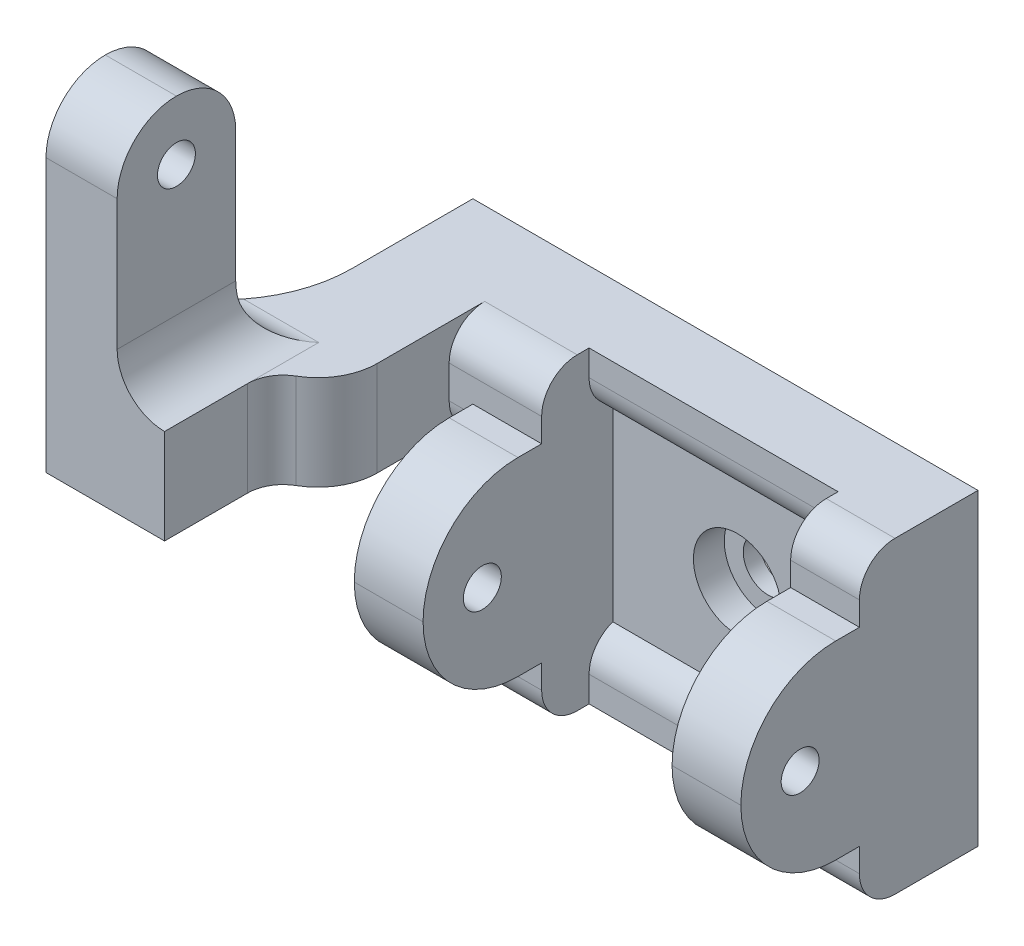
SolidWorks part; units mm, degrees
ref_plane "Front" through (0, 0, 0) normal (0, 0, 1) x (1, 0, 0)
ref_plane "Top" through (0, 0, 0) normal (0, 1, 0) x (1, 0, 0)
ref_plane "Right" through (0, 0, 0) normal (1, 0, 0) x (0, 0, -1)
sketch "Sketch1" plane through (0, 0, 0) normal (0, 0, 1) x (1, 0, 0)
  line L1 (0, 0) -> (-32.6, 0)
  line L2 (0, 0) -> (0, 26)
  line L3 (0, 26) -> (-32.6, 26)
  line L4 (-32.6, 0) -> (-32.6, 26)
  dimension "D1" = 32.6
  dimension "D2" = 26
extrude "Boss-Extrude1" add sketch "Sketch1" along normal blind 4
sketch "Sketch2" plane through (0, 0, 4) normal (0, 0, 1) x (1, 0, 0)
  line L0 (0, 26) -> (-32.6, 26) construction
  line L1 (0, 0) -> (0, 26) construction
  circle A0 centre (-16.3, 13) radius 3.7
  dimension "D1" = 7.4
  dimension "D2" = 13
  dimension "D3" = 16.3
extrude "Cut-Extrude1" cut sketch "Sketch2" against normal blind 2.6
sketch "Sketch3" plane through (0, 0, 1.4) normal (0, 0, 1) x (1, 0, 0)
  circle A0 centre (-16.3, 13) radius 2.1
  dimension "D1" = 4.2
extrude "Cut-Extrude2" cut sketch "Sketch3" against normal through all
sketch "Sketch4" plane through (0, 0, 4) normal (0, 0, 1) x (1, 0, 0)
  line L0 (-32.6, 0) -> (0, 0) construction
  line L1 (0, 26) -> (-5.8, 26)
  line L2 (0, 26) -> (0, 0)
  line L3 (0, 0) -> (-5.8, 0)
  line L4 (-5.8, 26) -> (-5.8, 0)
  line L6 (-32.6, 26) -> (-26.8, 26)
  line L7 (-32.6, 26) -> (-32.6, 0)
  line L8 (-32.6, 0) -> (-26.8, 0)
  line L9 (-26.8, 26) -> (-26.8, 0)
  dimension "D1" = 5.8
  dimension "D2" = 5.8
extrude "Boss-Extrude2" add sketch "Sketch4" along normal blind 16
sketch "Sketch5" plane through (0, 0, 0) normal (1, 0, 0) x (0, 0, -1)
  line L0 (-20, 0) -> (-20, 26) construction
  line L1 (-20, 0) -> (0, 0) construction
  circle A0 centre (-15, 13) radius 1.6
  dimension "D1" = 3.2
  dimension "D2" = 5
  dimension "D3" = 13
extrude "Cut-Extrude3" cut sketch "Sketch5" against normal through all
sketch "Sketch6" plane through (0, 0, 4) normal (0, 0, 1) x (1, 0, 0)
  line L1 (-26.8, 26) -> (-5.8, 26)
  line L2 (-26.8, 26) -> (-26.8, 21)
  line L3 (-26.8, 21) -> (-5.8, 21)
  line L4 (-5.8, 26) -> (-5.8, 21)
  line L5 (-26.8, 0) -> (-5.8, 0)
  line L6 (-26.8, 0) -> (-26.8, 5)
  line L7 (-26.8, 5) -> (-5.8, 5)
  line L8 (-5.8, 0) -> (-5.8, 5)
  dimension "D1" = 5
  dimension "D2" = 5
extrude "Boss-Extrude3" add sketch "Sketch6" along normal blind 2
sketch "Sketch7" plane through (-32.6, 0, 0) normal (-1, 0, 0) x (0, 0, 1)
  line L1 (20, 26) -> (10, 26)
  line L2 (20, 26) -> (20, 21)
  line L3 (20, 21) -> (10, 21)
  line L4 (10, 26) -> (10, 21)
  line L5 (20, 0) -> (10, 0)
  line L6 (20, 0) -> (20, 5)
  line L7 (20, 5) -> (10, 5)
  line L8 (10, 0) -> (10, 5)
  dimension "D1" = 10
  dimension "D2" = 10
  dimension "D3" = 5
  dimension "D4" = 5
extrude "Cut-Extrude4" cut sketch "Sketch7" against normal through all
fillet "Fillet1" radius 8 4 edges at (-2.9, 5, 20) (-2.9, 21, 20) (-29.7, 5, 20) (-29.7, 21, 20)
sketch "Sketch12" plane through (-32.6, 0, 0) normal (-1, 0, 0) x (0, 0, 1)
  line L0 (0, 26) -> (0, 0) construction
  line L1 (10, 26) -> (0, 26)
  line L2 (10, 26) -> (10, 18)
  line L3 (10, 18) -> (0, 18)
  line L4 (0, 26) -> (0, 18)
  dimension "D1" = 8
extrude "Boss-Extrude8" add sketch "Sketch12" along normal blind 10
sketch "Sketch13" plane through (0, 0, 10) normal (0, 0, 1) x (1, 0, 0)
  line L0 (-26.8, 26) -> (-42.6, 26) construction
  line L1 (-42.6, 18) -> (-34.6, 18)
  line L2 (-42.6, 18) -> (-42.6, 26)
  line L3 (-42.6, 26) -> (-34.6, 26)
  line L4 (-34.6, 18) -> (-34.6, 26)
  dimension "D1" = 8
extrude "Boss-Extrude9" add sketch "Sketch13" along normal blind 10
fillet "Fillet2" radius 3 4 edges at (-30.7, 26, 10) (-2.9, 26, 10) (-2.9, 0, 10) (-29.7, 0, 10)
sketch "Sketch14" plane through (0, 0, 20) normal (0, 0, 1) x (1, 0, 0)
  line L0 (-42.6, 18) -> (-34.6, 18) construction
  line L1 (-38.6, 18) -> (-48.6, 18)
  line L2 (-38.6, 18) -> (-38.6, 26)
  line L3 (-38.6, 26) -> (-48.6, 26)
  line L4 (-48.6, 18) -> (-48.6, 26)
  dimension "D1" = 8
  dimension "D2" = 10
extrude "Boss-Extrude10" add sketch "Sketch14" along normal blind 10
sketch "Sketch15" plane through (0, 26, 0) normal (0, 1, 0) x (1, 0, 0)
  line L1 (-48.6, -30) -> (-42.6, -30)
  line L2 (-48.6, -30) -> (-48.6, -20)
  line L3 (-48.6, -20) -> (-42.6, -20)
  line L4 (-42.6, -30) -> (-42.6, -20)
  dimension "D1" = 10
  dimension "D2" = 6
extrude "Boss-Extrude11" add sketch "Sketch15" along normal blind 20
fillet "Fillet10" radius 11 1 edges at (-42.6, 22, 20)
fillet "Fillet11" radius 3 1 edges at (-38.6, 22, 20)
fillet "Fillet12" radius 5 1 edges at (-34.6, 22, 20)
fillet "Fillet14" radius 4 1 edges at (-42.6, 26, 25)
fillet "Fillet15" radius 3 1 edges at (-43.6, 26, 20)
sketch "Sketch16" plane through (0, 0, 0) normal (0, 0, -1) x (-1, 0, 0)
  line L0 (42.6, 18) -> (32.6, 18)
  line L1 (32.6, 18) -> (32.6, 9)
  line L2 (32.6, 18) -> (32.6, 0) construction
  line L3 (32.6, 9) -> (42.6, 18)
  dimension "D1" = 9
extrude "Boss-Extrude12" add sketch "Sketch16" against normal blind 9
fillet "Fillet17" radius 3 1 edges at (-32.6, 9, 4.5)
fillet "Fillet18" radius 3 1 edges at (-33.6, 18, 10)
sketch "Sketch17" plane through (-48.6, 0, 0) normal (-1, 0, 0) x (0, 0, 1)
  line L0 (30, 46) -> (30, 18) construction
  line L1 (20, 46) -> (30, 46) construction
  circle A0 centre (25, 41) radius 1.6
  dimension "D1" = 3.2
  dimension "D2" = 5
  dimension "D3" = 5
extrude "Cut-Extrude5" cut sketch "Sketch17" against normal through all
fillet "Fillet19" radius 5 2 edges at (-45.6, 46, 20) (-45.6, 46, 30)
fillet "Fillet21" radius 3 2 edges at (-16.3, 21, 6) (-16.3, 5, 6)
